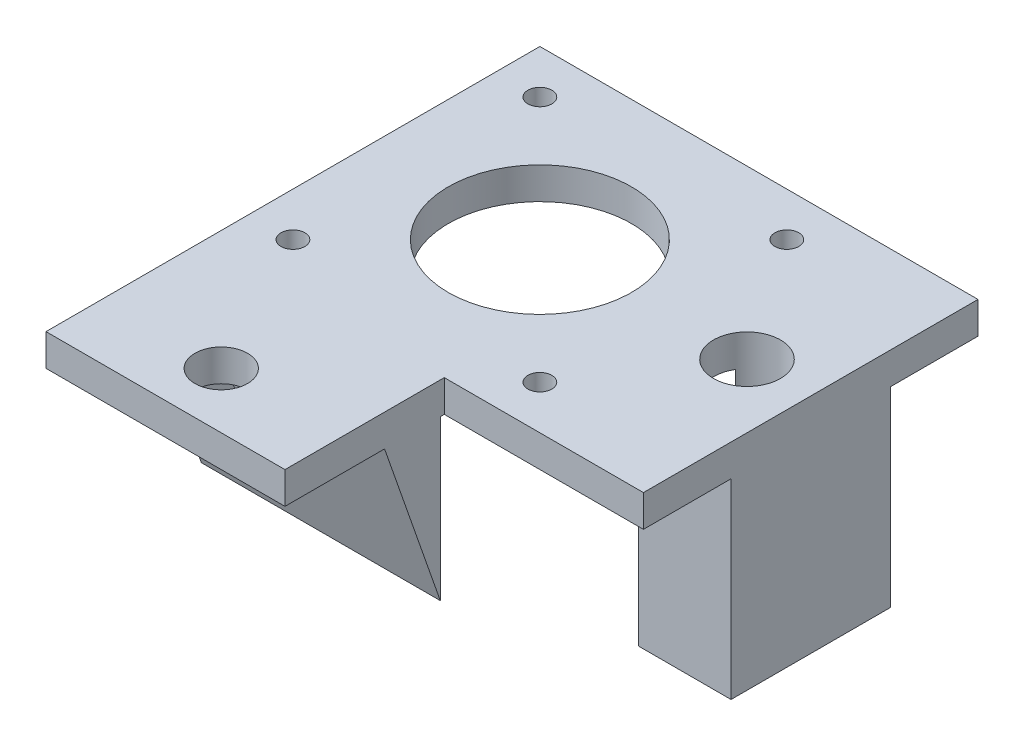
SolidWorks part; units mm, degrees
ref_plane "Front Plane" through (0, 0, 0) normal (0, 0, 1) x (1, 0, 0)
ref_plane "Top Plane" through (0, 0, 0) normal (0, 1, 0) x (1, 0, 0)
ref_plane "Right Plane" through (0, 0, 0) normal (1, 0, 0) x (0, 0, -1)
sketch "Sketch1" plane through (0, 0, 0) normal (0, 1, 0) x (1, 0, 0)
  line L0 (0, 21) -> (55, 21) construction
  line L2 (0, 0) -> (0, 42)
  line L3 (0, 42) -> (55, 42)
  line L4 (55, 0) -> (55, 42)
  line L5 (21, 42) -> (21, 0) construction
  line L6 (0, 0) -> (0, -20)
  line L7 (0, -20) -> (30, -20)
  line L8 (30, -20) -> (30, 0)
  line L9 (15, -20) -> (15, 0) construction
  line L13 (30, 0) -> (55, 0)
  line L14 (30, 0) -> (0, 0) construction
  circle A0 centre (47, 21) radius 4.2
  circle A1 centre (21, 21) radius 11.5
  circle A2 centre (5.5, 36.5) radius 1.5
  circle A3 centre (36.5, 36.5) radius 1.5
  circle A4 centre (5.5, 5.5) radius 1.5
  circle A5 centre (36.5, 5.5) radius 1.5
  circle A6 centre (15, -13) radius 3.3
  point P8 (55, 21)
  point P29 (15, 0)
  dimension "D2" = 23
  dimension "D4" = 8.4
  dimension "D9" = 3
  dimension "D13" = 6.6
  dimension "D1" = 26
  dimension "D3" = 42
  dimension "D5" = 21
  dimension "D6" = 55
  dimension "D7" = 15.5
  dimension "D8" = 15.5
  dimension "D10" = 30
  dimension "D11" = 20
  dimension "D12" = 13
extrude "Boss-Extrude1" add sketch "Sketch1" along normal blind 4
sketch "Sketch2" plane through (0, 0, 0) normal (0, -1, 0) x (1, 0, 0)
  line L1 (40.4, 0) -> (43.4, 0)
  line L2 (40.4, 0) -> (40.4, -42)
  line L3 (40.4, -42) -> (43.4, -42)
  line L4 (43.4, 0) -> (43.4, -42)
  line L5 (55, -42) -> (0, -42) construction
  line L6 (55, 0) -> (55, -42) construction
  line L7 (55, -11) -> (43.4, -11)
  line L8 (55, -11) -> (55, -31)
  line L9 (55, -31) -> (43.4, -31)
  line L10 (43.4, -11) -> (43.4, -31)
  line L11 (30, 0) -> (55, 0) construction
  circle A0 centre (47, -21) radius 6.6
  circle A1 centre (47, -21) radius 4.2
  circle A2 centre (47, -21) radius 4.2 construction
  point P10 (40.3, 0)
  point P25 (55, -21)
  point P26 (55, -21)
  circle M7 centre (47, -21) radius 4.2
  line M10 (55, -42) -> (55, 0)
  dimension "D1" = 2.4
  dimension "D2" = 3
  dimension "D3" = 20
extrude "Boss-Extrude2" add sketch "Sketch2" along normal blind 20 contours L4 A0 L10 M7 | A0 L10 L9 L7 L4 M10 region at (49.2, 0, -11.2312) region at (50.0669, 0, -15.3449)
sketch "Sketch3" plane through (0, -20, 0) normal (0, -1, 0) x (1, 0, 0)
  line L1 (55, -31) -> (43.4, -31)
  line L2 (55, -31) -> (55, -11)
  line L3 (55, -11) -> (43.4, -11)
  line L4 (43.4, -31) -> (43.4, -11)
extrude "Boss-Extrude3" add sketch "Sketch3" along normal blind 4
sketch "Sketch4" plane through (0, 0, 0) normal (-1, 0, 0) x (0, 0, 1)
  line L0 (-42, 0) -> (0.5, 0) construction
  line L1 (-42, 0) -> (20, 0) construction
  line L2 (0.5, 0) -> (7.5, 0)
  line L3 (7.5, 0) -> (0.5, -20)
  line L4 (0.5, -20) -> (0.5, 0)
  dimension "D1" = 42.5
  dimension "D2" = 7
  dimension "D3" = 20
extrude "Boss-Extrude4" add sketch "Sketch4" against normal up to surface (30 mm away) up to face at (30, 2, 10)
sketch "Sketch5" plane through (0, 0, 0) normal (0, -1, 0) x (1, 0, 0)
  circle A0 centre (15, 13) radius 8.75
  dimension "D1" = 17.5
extrude "Cut-Extrude1" cut sketch "Sketch5" along normal through all
equation "\"8mm hole\" = 8.4mm"
equation "\"22mm hole\"= 23mm"
equation "\"D2@Sketch1\"=\"22mm hole\""
equation "\"D4@Sketch1\"=\"8mm hole\""
equation "\"15mm hole\"= 15.8mm"
equation "\"D1@Sketch3\"= \"8mm hole\""
equation "\"bed height offset\"= 3mm"
equation "\"motor width\"= 42.5mm"
equation "\"D1@Sketch4\"= \"motor width\""
